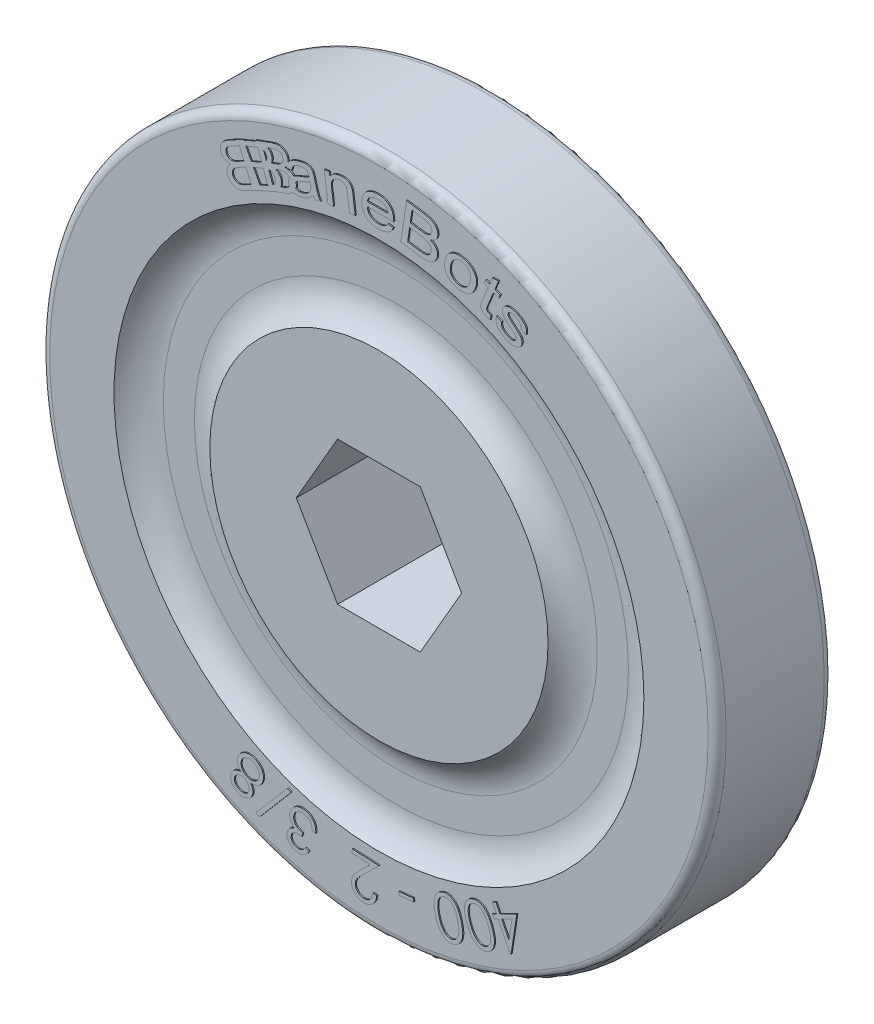
SolidWorks part; units mm, degrees
ref_plane "Front Plane" through (0, 0, 0) normal (0, 0, 1) x (1, 0, 0)
ref_plane "Top Plane" through (0, 0, 0) normal (0, 1, 0) x (1, 0, 0)
ref_plane "Right Plane" through (0, 0, 0) normal (1, 0, 0) x (0, 0, -1)
sketch "Sketch1" plane through (0, 0, 0) normal (0, 0, 1) x (1, 0, 0)
  line L1 (3.6662, -6.35) -> (7.3323, 0)
  line L2 (7.3323, 0) -> (3.6662, 6.35)
  line L3 (3.6662, 6.35) -> (-3.6662, 6.35)
  line L4 (-3.6662, 6.35) -> (-7.3323, 0)
  line L5 (-7.3323, 0) -> (-3.6662, -6.35)
  line L6 (-3.6662, -6.35) -> (3.6662, -6.35)
  circle A0 centre (0, 0) radius 6.35 construction
  circle A1 centre (0, 0) radius 30
  dimension "D2" = 60
extrude "Extrude1" add sketch "Sketch1" along normal mid plane 10.3
fillet "Fillet1" radius 0.8 2 edges at (30, 0, -5.15) (30, 0, 5.15)
sketch "Sketch2" plane through (0, 0, 0) normal (0, 1, 0) x (1, 0, 0)
  line L0 (0, 10.15) -> (0, 8.65)
  line L1 (0, 8.65) -> (-15, 8.65)
  line L2 (-15, 8.65) -> (-15, 3.65)
  line L3 (-15, 3.65) -> (-23.5, 3.65)
  line L4 (-23.5, 3.65) -> (-23.5, 10.14)
  line L5 (-23.5, 10.14) -> (-28.5, 10.14)
  line L6 (-28.5, 10.14) -> (-28.5, 10.15)
  line L8 (-28.5, 10.15) -> (0, 10.15)
  dimension "D1" = 0.01
  dimension "D2" = 15
  dimension "D3" = 23.5
  dimension "D4" = 6.5
  dimension "D5" = 1.5
  dimension "D6" = 28.5
revolve "Cut-Revolve1" cut sketch "Sketch2" angle 360 about L0
fillet "Fillet3" radius 3.5 2 edges at (-15, 0, -3.65) (-23.5, 0, -3.65)
mirror "Mirror1" about plane through (0, 0, 0) normal (0, 0, 1) of "Fillet3", "Cut-Revolve1"
sketch "Sketch4" plane through (0, 0, -5.15) normal (0, 0, -1) x (-1, 0, 0)
  line L0 (0, 0) -> (-7.7865, 23.2297) construction
  line L1 (-11.3283, 21.7237) -> (-13.5014, 25.8911) construction
  line L3 (0, 0) -> (13.0638, 20.7265) construction
  line L4 (0, 0) -> (0, 28.5) construction
  line L5 (0, 0) -> (-13.0638, 20.7265) construction
  line L6 (0, -24.5) -> (0, 0) construction
  arc A0 (13.0638, 20.7265) -> (-7.7865, 23.2297) centre (0, 0) ccw construction
  arc A1 (-9.5171, 22.576) -> (-13.0638, 20.7265) centre (0, 0) ccw construction
  arc A5 (12.7, -20.9514) -> (-12.7, -20.9514) centre (0, 0) cw construction
  text T0 "BaneBots" font "Arial" height 3.5
  text T1 "400 - 2  3/8" font "Century Gothic" height 3.5
  dimension "D1" = 24.5
  dimension "D2" = 21
  dimension "D3" = 4
  dimension "D4" = 1.85
  dimension "D5" = 25.4
extrude "Extrude3" add sketch "Sketch4" along normal blind 0.1
sketch "Sketch5" plane through (0, 0, -5.15) normal (0, 0, -1) x (-1, 0, 0)
  text T0 "B" font "Arial" height 3.5
extrude "Extrude4" add sketch "Sketch5" along normal blind 0.1
ref_plane "Plane1" through (0, 0, 0) normal (0.8867, -0.4624, 0) x (0, 0, -1)
mirror "Mirror2" about plane through (0, 0, 0) normal (0.8867, -0.4624, 0) of "Extrude4"
sketch "Sketch6" plane through (0, 0, 5.15) normal (0, 0, 1) x (1, 0, 0)
  line L0 (0, 0) -> (0, 28.5) construction
  arc A0 (-13.0638, 20.7265) -> (-6.6695, 23.5747) centre (0, 0) cw construction
  arc A1 (7.7865, 23.2297) -> (-13.0638, 20.7265) centre (0, 0) ccw construction
  arc A2 (13.0638, 20.7265) -> (-11.9271, 21.4008) centre (0, 0) ccw construction
  arc A6 (-12.7, -20.9514) -> (12.7, -20.9514) centre (0, 0) ccw
  arc A7 (-12.7, -20.9514) -> (12.7, -20.9514) centre (0, 0) ccw construction
  text T0 "BaneBots" font "Arial" height 3.5
  text T1 "400 - 2  3/8" font "Century Gothic" height 3.5
  dimension "D1" = 7
  dimension "D3" = 0
  dimension "D2" = 25
extrude "Extrude5" add sketch "Sketch6" along normal blind 0.1
sketch "Sketch7" plane through (0, 0, 5.15) normal (0, 0, 1) x (1, 0, 0)
  line L0 (-9.9689, 22.3801) -> (-11.8813, 26.6735) construction
  arc A2 (-6.6695, 23.5747) -> (-13.0638, 20.7265) centre (0, 0) ccw construction
  circle A3 centre (0, 0) radius 29.2 construction
  text T0 "B" font "Arial" height 3.5
extrude "Extrude6" add sketch "Sketch7" along normal blind 0.1
ref_plane "Plane2" through (0, 0, 0) normal (0.9135, 0.4069, 0) x (0, 0, -1)
mirror "Mirror3" about plane through (0, 0, 0) normal (0.9135, 0.4069, 0) of "Extrude6"
